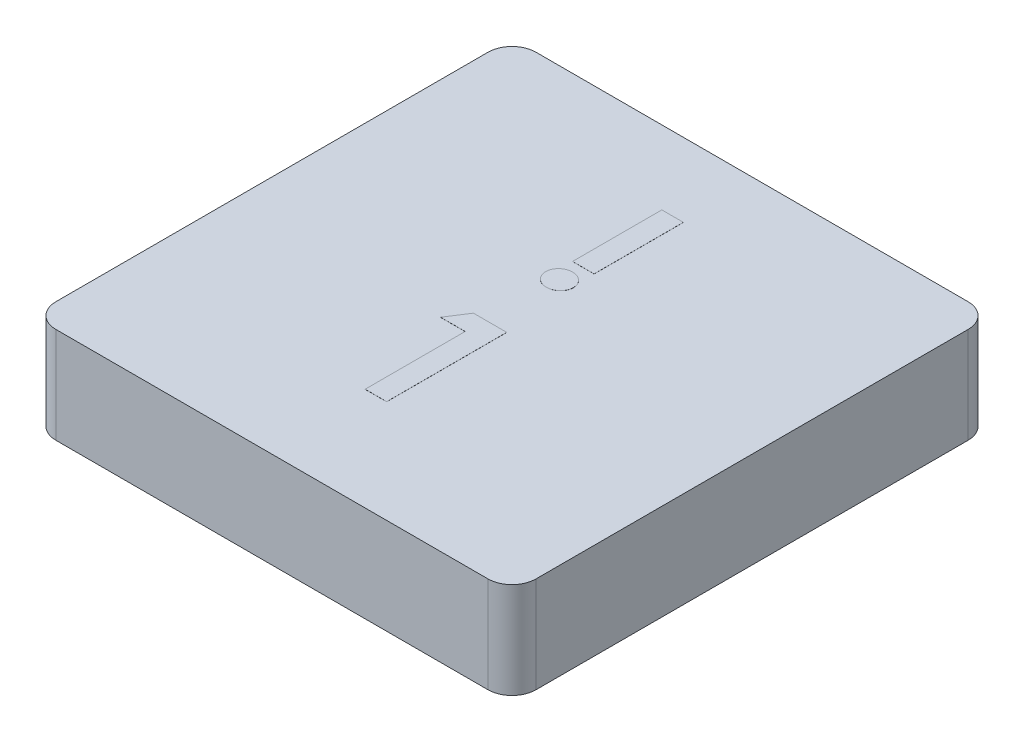
SolidWorks part; units mm, degrees
ref_plane "Front Plane" through (0, 0, 0) normal (0, 0, 1) x (1, 0, 0)
ref_plane "Top Plane" through (0, 0, 0) normal (0, 1, 0) x (1, 0, 0)
ref_plane "Right Plane" through (0, 0, 0) normal (1, 0, 0) x (0, 0, -1)
sketch "Sketch1" plane through (0, 0, 0) normal (0, 1, 0) x (1, 0, 0)
  line L0 (0, 0) -> (12.7, 0)
  line L1 (12.7, 0) -> (12.7, 12.7)
  line L2 (12.7, 12.7) -> (0, 12.7)
  line L3 (0, 12.7) -> (0, 0)
  dimension "D1" = 12.7
  dimension "D2" = 12.7
extrude "Boss-Extrude1" add sketch "Sketch1" along normal blind 2.54
fillet "Fillet1" radius 0.635 4 edges at (0, 1.27, -12.7) (12.7, 1.27, -12.7) (12.7, 1.27, 0) (0, 1.27, 0)
shell "Shell1" thickness 0.635 removed face at (6.35, 0, -6.35)
sketch "Sketch2" plane through (0, 1.905, 0) normal (0, -1, 0) x (-1, 0, 0)
  line L0 (-0.635, 6.35) -> (-12.065, 6.35) construction
  line L1 (-0.635, 12.065) -> (-0.635, 0.635) construction
  line L2 (-12.065, 0.635) -> (-12.065, 12.065) construction
  line L3 (-6.35, 0.635) -> (-6.35, 12.065) construction
  line L4 (-0.635, 0.635) -> (-12.065, 0.635) construction
  line L5 (-12.065, 12.065) -> (-0.635, 12.065) construction
  circle A0 centre (-6.35, 6.35) radius 2.54
  dimension "D1" = 5.08
extrude "Boss-Extrude2" add sketch "Sketch2" along normal up to surface (1.905 mm away) up to face at (6.35, 0, -6.35)
sketch "Sketch4" plane through (0, 2.54, 0) normal (0, 1, 0) x (1, 0, 0)
  line L0 (0, 12.065) -> (0, 0.635) construction
  line L1 (12.065, 12.7) -> (0.635, 12.7) construction
  line L2 (0.635, 0) -> (12.065, 0) construction
  text T0 "<b>1</b>"
  text T1 "<b>!</b>"
  dimension "D1" = 5.588
  dimension "D2" = 5.08
  dimension "D3" = 5.207
  dimension "D4" = 2.7178
extrude "Boss-Extrude4" add sketch "Sketch4" along normal blind 0.0025
